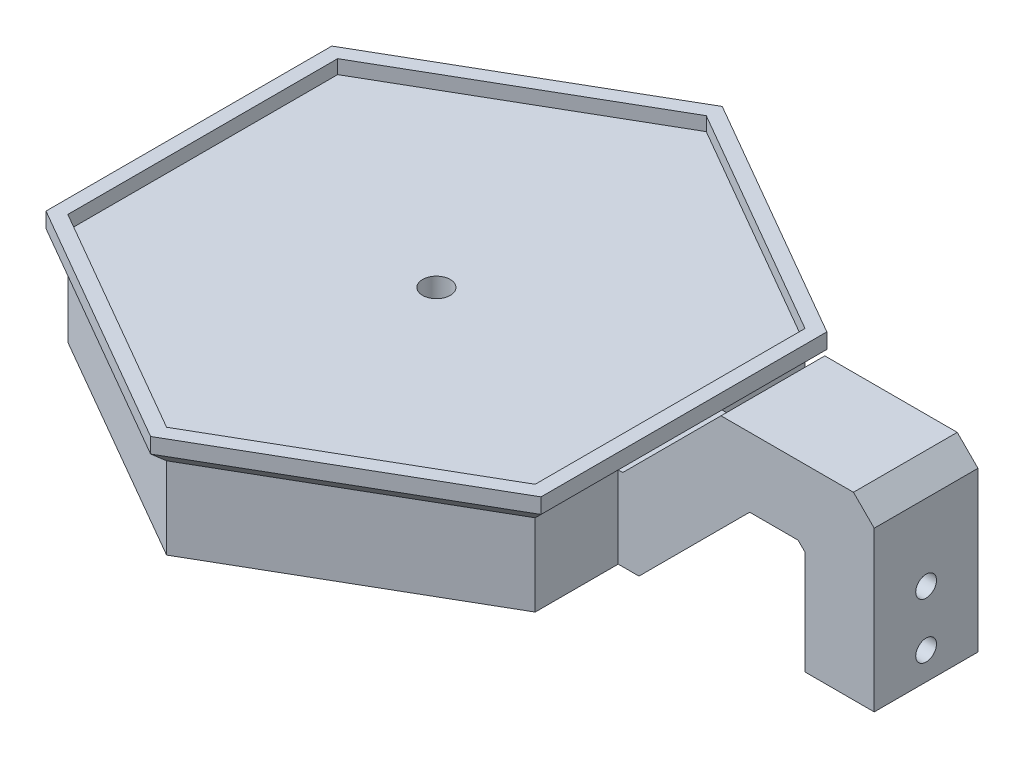
SolidWorks part; units mm, degrees
ref_plane "Front" through (0, 0, 0) normal (0, 0, 1) x (1, 0, 0)
ref_plane "Top" through (0, 0, 0) normal (0, 1, 0) x (1, 0, 0)
ref_plane "Right" through (0, 0, 0) normal (1, 0, 0) x (0, 0, -1)
sketch "Sketch1" plane through (0, 0, 0) normal (0, 1, 0) x (1, 0, 0)
  line L1 (33.775, 19.5) -> (0, 39)
  line L2 (0, 39) -> (-33.775, 19.5)
  line L3 (-33.775, 19.5) -> (-33.775, -19.5)
  line L4 (-33.775, -19.5) -> (0, -39)
  line L5 (0, -39) -> (33.775, -19.5)
  line L6 (33.775, -19.5) -> (33.775, 19.5)
  circle A0 centre (0, 0) radius 33.775 construction
  dimension "D1" = 78
extrude "Boss-Extrude1" add sketch "Sketch1" along normal blind 14
sketch "Sketch2" plane through (0, 14, 0) normal (0, 1, 0) x (1, 0, 0)
  line L0 (0, 41.3094) -> (-35.775, 20.6547)
  line L1 (-35.775, 20.6547) -> (-35.775, -20.6547)
  line L2 (-35.775, -20.6547) -> (0, -41.3094)
  line L3 (0, -41.3094) -> (35.775, -20.6547)
  line L4 (35.775, -20.6547) -> (35.775, 20.6547)
  line L5 (35.775, 20.6547) -> (0, 41.3094)
  line L6 (33.775, -19.5) -> (33.775, 19.5)
  line L7 (33.775, 19.5) -> (0, 39)
  line L8 (0, 39) -> (-33.775, 19.5)
  line L9 (-33.775, 19.5) -> (-33.775, -19.5)
  line L10 (-33.775, -19.5) -> (0, -39)
  line L11 (0, -39) -> (33.775, -19.5)
  line L12 (33.775, -19.5) -> (33.775, 19.5)
  line L13 (33.775, 19.5) -> (0, 39)
  line L14 (0, 39) -> (-33.775, 19.5)
  line L15 (-33.775, 19.5) -> (-33.775, -19.5)
  line L16 (-33.775, -19.5) -> (0, -39)
  line L17 (0, -39) -> (33.775, -19.5)
  dimension "D1" = 0
  dimension "D2" = 2
extrude "Boss-Extrude2" add sketch "Sketch2" along normal blind 2 and the other way blind 0.2
chamfer "Chamfer1" distance 2 angle 45 6 edges at (-33.775, 13.8, 0) (-16.8875, 13.8, -29.25) (16.8875, 13.8, -29.25) (33.775, 13.8, 0) (16.8875, 13.8, 29.25) (-16.8875, 13.8, 29.25)
sketch "Sketch3" plane through (0, 14, 0) normal (0, 1, 0) x (1, 0, 0)
  circle A0 centre (0, 0) radius 2
  dimension "D1" = 4
extrude "Cut-Extrude1" cut sketch "Sketch3" against normal through all
sketch "Sketch5" plane through (0, 0, 0) normal (0, 0, 1) x (1, 0, 0)
  line L0 (33.775, 11.8) -> (34.4329, 11.8)
  line L1 (33.775, 11.8) -> (33.775, 0) construction
  line L2 (34.4329, 11.8) -> (48.6329, 26)
  line L3 (33.775, 0) -> (36.775, 0)
  line L4 (48.6329, 26) -> (70.775, 26)
  line L5 (60.775, 0) -> (60.775, 16)
  line L6 (70.775, 26) -> (70.775, 0)
  line L7 (70.775, 0) -> (60.775, 0)
  line L8 (33.775, 11.8) -> (0, 11.8) construction
  line L9 (60.775, 16) -> (52.775, 16)
  line L10 (52.775, 16) -> (36.775, 0)
  line L11 (33.775, 11.8) -> (35.775, 13.8) construction
  line L12 (33.775, 0) -> (33.775, 11.8)
  point P10 (74.1426, -2.4739)
  point P13 (71.3193, -6.8853)
  point P15 (83.5096, 28.8686)
  dimension "D1" = 10
  dimension "D2" = 10
  dimension "D3" = 16
  dimension "D4" = 26
  dimension "D5" = 135
  dimension "D7" = 8
  dimension "D8" = 3
extrude "Boss-Extrude3" add sketch "Sketch5" along normal mid plane 15
sketch "Sketch6" plane through (60.775, 0, 0) normal (-1, 0, 0) x (0, 0, 1)
  line L0 (-7.5, 0) -> (7.5, 16) construction
  circle A0 centre (0, 12) radius 1.5
  circle A1 centre (0, 4) radius 1.5
  point P4 (0, 8)
  dimension "D1" = 3
  dimension "D2" = 3
  dimension "D3" = 4
  dimension "D4" = 4
extrude "Cut-Extrude2" cut sketch "Sketch6" against normal up to next
chamfer "Chamfer2" distance 1 angle 45 1 edges at (60.775, 16, 0)
chamfer "Chamfer3" distance 3 angle 45 1 edges at (70.775, 26, 0)
